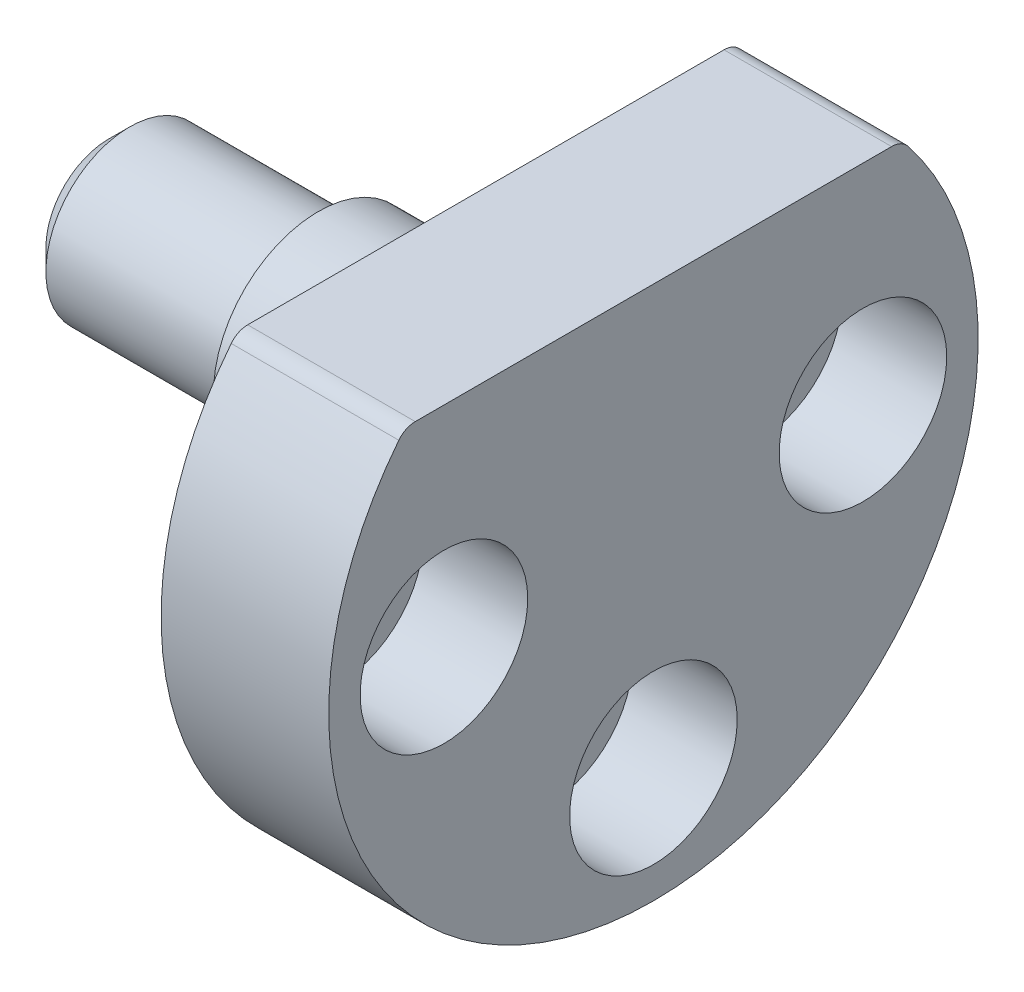
SolidWorks part; units mm, degrees
material "AISI 304"
ref_plane "Front Plane" through (0, 0, 0) normal (0, 0, 1) x (1, 0, 0)
ref_plane "Top Plane" through (0, 0, 0) normal (0, 1, 0) x (1, 0, 0)
ref_plane "Right Plane" through (0, 0, 0) normal (1, 0, 0) x (0, 0, -1)
sketch "Sketch1" plane through (0, 0, 0) normal (1, 0, 0) x (0, 0, -1)
  line L0 (-5.9214, 5) -> (5.9214, 5)
  arc A0 (-5.9214, 5) -> (5.9214, 5) centre (0, 0) ccw
  circle A1 centre (0, 0) radius 2.5
  circle A2 centre (-5, 0) radius 1
  circle A3 centre (5, 0) radius 1
  circle A4 centre (0, -5) radius 1
  circle A5 centre (0, 0) radius 2
  dimension "D1" = 15.5
  dimension "D3" = 2
  dimension "D5" = 5
  dimension "D6" = 5
  dimension "D7" = 5
  dimension "D8" = 4
  dimension "D9" = 2
  dimension "D2" = 5
  dimension "D4" = 5
extrude "Boss-Extrude1" add sketch "Sketch1" along normal blind 4 contours L0 A0
extrude "Cut-Extrude2" cut sketch "Sketch1<3>" along normal blind 4 contours A2 | A3 | A4
sketch "Sketch1<3>" plane through (0, 0, 0) normal (1, 0, 0) x (0, 0, -1) same geometry as "Sketch1"
extrude "Boss-Extrude2" add sketch "Sketch1<4>" against normal blind 4 contours A1
sketch "Sketch1<4>" plane through (0, 0, 0) normal (1, 0, 0) x (0, 0, -1) same geometry as "Sketch1"
extrude "Boss-Extrude3" add sketch "Sketch1<5>" against normal blind 9 contours A5
sketch "Sketch1<5>" plane through (0, 0, 0) normal (1, 0, 0) x (0, 0, -1) same geometry as "Sketch1"
chamfer "Chamfer1" distance 0.5 angle 45 1 edges at (-9, 0, -2)
fillet "Fillet1" radius 0.5 2 edges at (2, 5, -5.9214) (2, 5, 5.9214)
sketch "Sketch2" plane through (4, 0, 0) normal (1, 0, 0) x (0, 0, -1)
  circle A0 centre (-5, 0) radius 2
  circle A1 centre (5, 0) radius 2
  circle A2 centre (0, -5) radius 2
  dimension "D1" = 4
extrude "Cut-Extrude3" cut sketch "Sketch2" against normal blind 2.5
